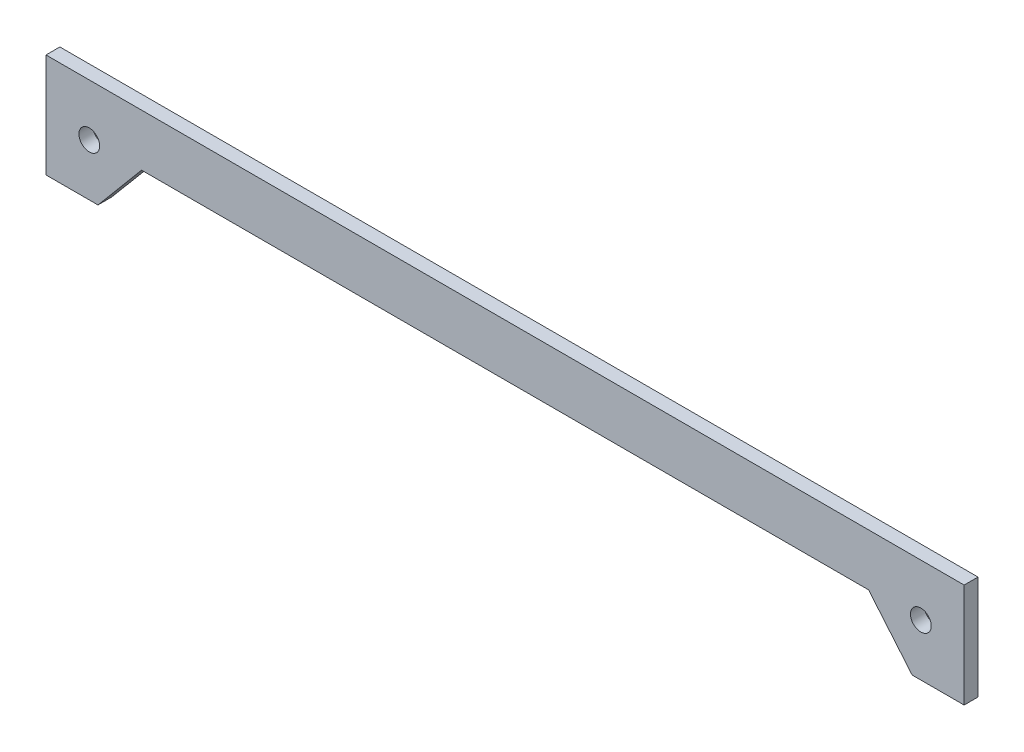
SolidWorks part; units mm, degrees
material "Pappelsperrholz"
ref_plane "Ebene vorne" through (0, 0, 0) normal (0, 0, 1) x (1, 0, 0)
ref_plane "Ebene oben" through (0, 0, 0) normal (0, 1, 0) x (1, 0, 0)
ref_plane "Ebene rechts" through (0, 0, 0) normal (1, 0, 0) x (0, 0, -1)
sketch "Skizze1" plane through (0, 0, 0) normal (0, 0, 1) x (1, 0, 0)
  line L0 (0, 0) -> (0, -22.0536) construction
  line L1 (132.5, 0) -> (-132.5, 0)
  line L2 (-132.5, 0) -> (-132.5, -30)
  line L3 (-132.5, -30) -> (-117.5, -30)
  line L4 (-117.5, -30) -> (-104.9135, -15)
  line L5 (-104.9135, -15) -> (104.9135, -15)
  line L6 (117.5, -30) -> (104.9135, -15)
  line L7 (132.5, -30) -> (117.5, -30)
  line L8 (132.5, 0) -> (132.5, -30)
  point P9 (0, -15)
  dimension "D1" = 265
  dimension "D2" = 30
  dimension "D3" = 15
  dimension "D4" = 15
  dimension "D5" = 130
extrude "Grundplatte" add sketch "Skizze1" along normal blind 4
sketch "Skizze2" plane through (0, 0, 4) normal (0, 0, 1) x (1, 0, 0)
  line L0 (0, 0) -> (0, -15) construction
  line L1 (-104.9135, -15) -> (104.9135, -15) construction
  line L2 (132.5, 0) -> (-132.5, 0) construction
  circle A0 centre (-120, -15) radius 3
  circle A1 centre (120, -15) radius 3
  dimension "D1" = 6
  dimension "D3" = 240
  dimension "D2" = 15
extrude "Schnitt-Linear austragen1" cut sketch "Skizze2" against normal through all
